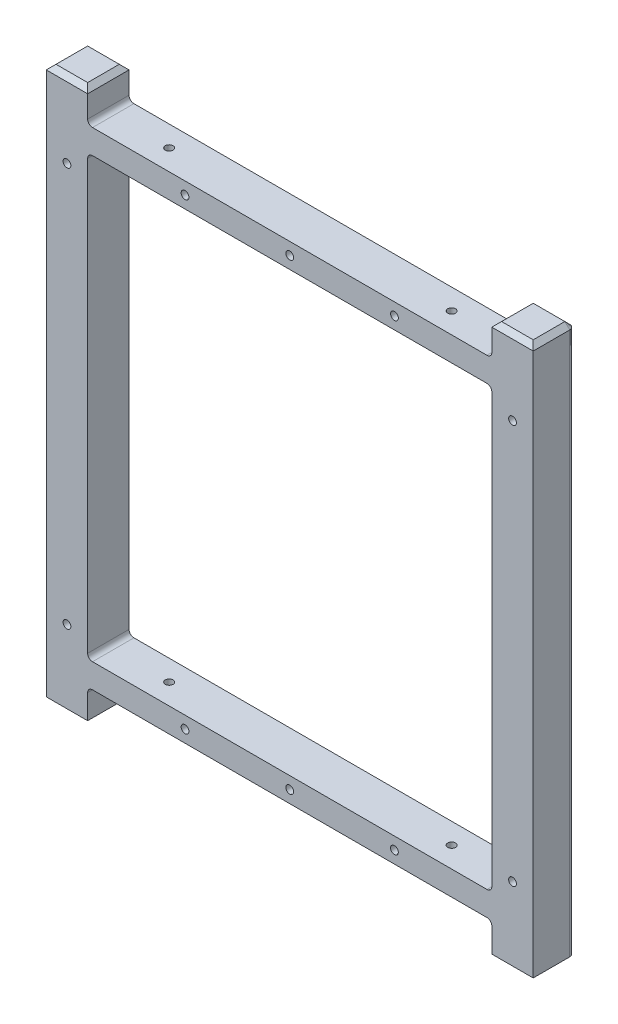
SolidWorks part; units mm, degrees
material "5052-H34"
ref_plane "Frontal" through (0, 0, 0) normal (0, 0, 1) x (1, 0, 0)
ref_plane "Superior" through (0, 0, 0) normal (0, 1, 0) x (1, 0, 0)
ref_plane "Direito" through (0, 0, 0) normal (1, 0, 0) x (0, 0, -1)
sketch "Sketch1" plane through (0, 0, 0) normal (0, 0, 1) x (1, 0, 0)
  line L1 (-50, -56.75) -> (50, -56.75)
  line L2 (-50, -56.75) -> (-50, 56.75)
  line L3 (-50, 56.75) -> (50, 56.75)
  line L4 (50, -56.75) -> (50, 56.75)
  line L5 (-50, -56.75) -> (50, 56.75) construction
  line L6 (-50, 56.75) -> (50, -56.75) construction
  point P0 (0, 0)
  dimension "D1" = 113.5
  dimension "D2" = 100
extrude "Boss-Extrude1" add sketch "Sketch1" along normal mid plane 8.5
sketch "Sketch4" plane through (0, 0, 4.25) normal (0, 0, 1) x (1, 0, 0)
  line L0 (-50, 56.75) -> (-50, -56.75) construction
  line L1 (-40.5, -44.75) -> (40.5, -44.75)
  line L2 (-41.5, -43.75) -> (-41.5, 44.25)
  line L3 (-40.5, 45.25) -> (40.5, 45.25)
  line L4 (41.5, -43.75) -> (41.5, 44.25)
  line L5 (-40.5, -43.75) -> (40.5, 44.25) construction
  line L6 (-40.5, 44.25) -> (40.5, -43.75) construction
  line L7 (50, 56.75) -> (-50, 56.75) construction
  line L8 (-41.5, 56.75) -> (41.5, 56.75)
  line L9 (-41.5, 56.75) -> (-41.5, 51.25)
  line L10 (-40.5, 50.25) -> (40.5, 50.25)
  line L11 (41.5, 56.75) -> (41.5, 51.25)
  line L12 (-50, -56.75) -> (50, -56.75) construction
  line L13 (-41.5, -56.75) -> (41.5, -56.75)
  line L14 (-41.5, -56.75) -> (-41.5, -50.75)
  line L15 (-40.5, -49.75) -> (40.5, -49.75)
  line L16 (41.5, -56.75) -> (41.5, -50.75)
  line L17 (50, -56.75) -> (50, 56.75) construction
  arc A0 (-41.5, 51.25) -> (-40.5, 50.25) centre (-40.5, 51.25) ccw
  arc A1 (40.5, 50.25) -> (41.5, 51.25) centre (40.5, 51.25) ccw
  arc A2 (-40.5, 45.25) -> (-41.5, 44.25) centre (-40.5, 44.25) ccw
  arc A3 (40.5, 45.25) -> (41.5, 44.25) centre (40.5, 44.25) cw
  arc A4 (41.5, -43.75) -> (40.5, -44.75) centre (40.5, -43.75) cw
  arc A5 (-40.5, -44.75) -> (-41.5, -43.75) centre (-40.5, -43.75) cw
  arc A6 (-40.5, -49.75) -> (-41.5, -50.75) centre (-40.5, -50.75) ccw
  arc A7 (40.5, -49.75) -> (41.5, -50.75) centre (40.5, -50.75) cw
  point P0 (1.8681, -1.8902)
  dimension "D11" = 1
  dimension "D12" = 1
  dimension "D13" = 1
  dimension "D14" = 1
  dimension "D15" = 1
  dimension "D16" = 1
  dimension "D17" = 1
  dimension "D18" = 1
  dimension "D1" = 8.5
  dimension "D2" = 8.5
  dimension "D3" = 8.5
  dimension "D4" = 6.5
  dimension "D5" = 8.5
  dimension "D6" = 8.5
  dimension "D7" = 7
  dimension "D8" = 5
  dimension "D9" = 5
  dimension "D10" = 8.5
extrude "Cut-Extrude1" cut sketch "Sketch4" against normal through all
hole_wizard "M2 Hole1-C" positions "Sketch6" profile "Sketch5" hole size "M2" standard "DIN"
sketch "Sketch6" plane through (0, 0, 4.25) normal (0, 0, 1) x (1, 0, 0)
  line L0 (-50, 56.75) -> (-50, -56.75) construction
  line L1 (50, -56.75) -> (50, 56.75) construction
  line L2 (-40.5, 50.25) -> (40.5, 50.25) construction
  line L3 (40.5, -49.75) -> (-40.5, -49.75) construction
  point P0 (-45.75, -40.75)
  point P2 (45.75, -40.75)
  point P4 (-45.75, 41.25)
  point P6 (45.75, 41.25)
  dimension "D1" = 4.25
  dimension "D2" = 4.25
  dimension "D3" = 9
  dimension "D4" = 9
sketch "Sketch5" plane through (-45.75, -40.75, 4.25) normal (1, 0, 0) x (0, -1, 0)
  line L0 (0, 0) -> (0, 3.4807)
  line L1 (0, 3.4807) -> (0.8, 3)
  line L2 (0.8, 3) -> (0.8, 0)
  line L5 (0.8, 0) -> (0, 0)
  line L10 (0, 3.4807) -> (-0.8, 3) construction
  line L11 (0, -6.35) -> (0, 107.95) construction
  dimension "Hole Dia." = 1.6
  dimension "Hole Depth" = 3
  dimension "Drill Angle" = 118
hole_wizard "M2 Hole2-D" positions "Sketch26" profile "Sketch24" hole size "M2" standard "DIN"
sketch "Sketch26" plane through (0, 0, 4.25) normal (0, 0, 1) x (1, 0, 0)
  line L0 (40.5, 45.25) -> (-40.5, 45.25) construction
  line L1 (-50, 56.75) -> (-50, -56.75) construction
  line L2 (50, -56.75) -> (50, 56.75) construction
  line L3 (-40.5, -44.75) -> (40.5, -44.75) construction
  point P0 (-21.5, 47.75)
  point P2 (21.5, 47.75)
  point P4 (-21.5, -47.25)
  point P6 (21.5, -47.25)
  dimension "D1" = 2.5
  dimension "D2" = 28.5
  dimension "D3" = 28.5
  dimension "D4" = 2.5
sketch "Sketch24" plane through (-21.5, 47.75, 4.25) normal (1, 0, 0) x (0, -1, 0)
  line L0 (0, 0) -> (0, 5.4807)
  line L1 (0, 5.4807) -> (0.8, 5)
  line L2 (0.8, 5) -> (0.8, 0)
  line L5 (0.8, 0) -> (0, 0)
  line L10 (0, 5.4807) -> (-0.8, 5) construction
  line L11 (0, -6.35) -> (0, 107.95) construction
  dimension "Hole Dia." = 1.6
  dimension "Hole Depth" = 5
  dimension "Drill Angle" = 118
hole_wizard "M2 Hole3-E" positions "Sketch13" profile "Sketch12" hole size "M2" standard "DIN"
sketch "Sketch13" plane through (0, 0, 4.25) normal (0, 0, 1) x (1, 0, 0)
  line L0 (40.5, -49.75) -> (-40.5, -49.75) construction
  line L1 (-40.5, 50.25) -> (40.5, 50.25) construction
  point P0 (0, 47.75)
  point P2 (0, -47.25)
  dimension "D1" = 2.5
  dimension "D2" = 2.5
sketch "Sketch12" plane through (0, 47.75, 4.25) normal (1, 0, 0) x (0, -1, 0)
  line L0 (0, 0) -> (0, 4.4807)
  line L1 (0, 4.4807) -> (0.8, 4)
  line L2 (0.8, 4) -> (0.8, 0)
  line L5 (0.8, 0) -> (0, 0)
  line L10 (0, 4.4807) -> (-0.8, 4) construction
  line L11 (0, -6.35) -> (0, 107.95) construction
  dimension "Hole Dia." = 1.6
  dimension "Hole Depth" = 4
  dimension "Drill Angle" = 118
hole_wizard "M2 Hole4-F" positions "Sketch23" profile "Sketch22" hole size "M2" standard "DIN"
sketch "Sketch23" plane through (0, 50.25, 0) normal (0, 1, 0) x (1, 0, 0)
  line L0 (-40.5, 4.25) -> (40.5, 4.25) construction
  line L1 (-41.5, 4.25) -> (-41.5, -4.25) construction
  line L2 (41.5, 4.25) -> (41.5, -4.25) construction
  point P0 (-29, 0)
  point P2 (29, 0)
  dimension "D1" = 4.25
  dimension "D2" = 12.5
  dimension "D3" = 12.5
sketch "Sketch22" plane through (-29, 50.25, 0) normal (1, 0, 0) x (0, 0, 1)
  line L0 (0, 0) -> (0, 10.4807)
  line L1 (0, 10.4807) -> (0.8, 10)
  line L2 (0.8, 10) -> (0.8, 0)
  line L5 (0.8, 0) -> (0, 0)
  line L10 (0, 10.4807) -> (-0.8, 10) construction
  line L11 (0, -6.35) -> (0, 107.95) construction
  dimension "Hole Dia." = 1.6
  dimension "Hole Depth" = 10
  dimension "Drill Angle" = 118
hole_wizard "M2 Hole5-G" positions "Sketch17" profile "Sketch16" hole size "M2" standard "DIN"
sketch "Sketch17" plane through (0, -49.75, 0) normal (0, -1, 0) x (-1, 0, 0)
  line L0 (41.5, 4.25) -> (41.5, -4.25) construction
  line L1 (-41.5, 4.25) -> (-41.5, -4.25) construction
  line L2 (-40.5, -4.25) -> (40.5, -4.25) construction
  point P0 (29, 0)
  point P2 (-29, 0)
  dimension "D1" = 12.5
  dimension "D2" = 12.5
  dimension "D3" = 4.25
sketch "Sketch16" plane through (-29, -49.75, 0) normal (1, 0, 0) x (0, 0, -1)
  line L0 (0, 0) -> (0, 10.4807)
  line L1 (0, 10.4807) -> (0.8, 10)
  line L2 (0.8, 10) -> (0.8, 0)
  line L5 (0.8, 0) -> (0, 0)
  line L10 (0, 10.4807) -> (-0.8, 10) construction
  line L11 (0, -6.35) -> (0, 107.95) construction
  dimension "Hole Dia." = 1.6
  dimension "Hole Depth" = 10
  dimension "Drill Angle" = 118
hole_wizard "M2 Hole6-H" positions "Sketch21" profile "Sketch20" hole size "M2" standard "DIN"
sketch "Sketch21" plane through (0, 0, -4.25) normal (0, 0, -1) x (-1, 0, 0)
  line L0 (40.5, 50.25) -> (-40.5, 50.25) construction
  line L1 (-41.5, 51.25) -> (-41.5, 56.75) construction
  line L2 (41.5, 56.75) -> (41.5, 51.25) construction
  line L3 (-40.5, -49.75) -> (40.5, -49.75) construction
  point P0 (-35.5, 47.75)
  point P2 (35.5, 47.75)
  point P4 (-35.5, -47.25)
  point P6 (35.5, -47.25)
  dimension "D1" = 2.5
  dimension "D2" = 6
  dimension "D3" = 6
  dimension "D4" = 2.5
sketch "Sketch20" plane through (35.5, 47.75, -4.25) normal (1, 0, 0) x (0, 1, 0)
  line L0 (0, 0) -> (0, 5.4807)
  line L1 (0, 5.4807) -> (0.8, 5)
  line L2 (0.8, 5) -> (0.8, 0)
  line L5 (0.8, 0) -> (0, 0)
  line L10 (0, 5.4807) -> (-0.8, 5) construction
  line L11 (0, -6.35) -> (0, 107.95) construction
  dimension "Hole Dia." = 1.6
  dimension "Hole Depth" = 5
  dimension "Drill Angle" = 118
fillet "Fillet1" radius 1 2 edges at (-50, 0, -4.25) (50, 0, -4.25)
chamfer "Chamfer1" distance 1 angle 45 20 edges at (-41.5, -56.75, 0) (-45.75, -56.75, 4.25) (-50, -56.75, 0.5) (-49.7071, -56.75, -3.9571) (-45.25, -56.75, -4.25) (-45.75, 56.75, 4.25) (-50, 56.75, 0.5) (-49.7071, 56.75, -3.9571) (-45.25, 56.75, -4.25) (-41.5, 56.75, 0) (45.75, -56.75, 4.25) (41.5, -56.75, 0) (45.25, -56.75, -4.25) (49.7071, -56.75, -3.9571) (50, -56.75, 0.5) (49.7071, 56.75, -3.9571) (50, 56.75, 0.5) (45.75, 56.75, 4.25) (41.5, 56.75, 0) (45.25, 56.75, -4.25)
